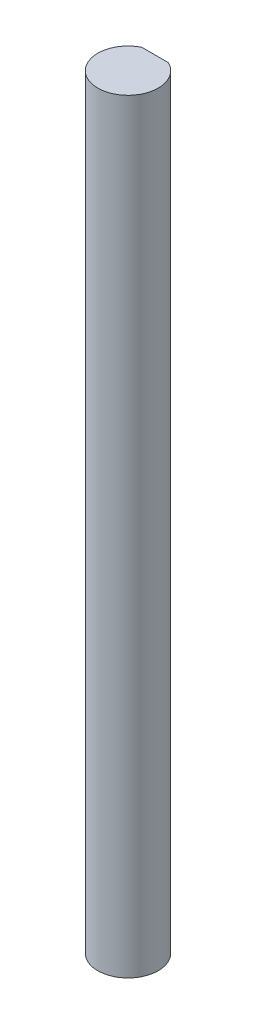
SolidWorks part; units mm, degrees
ref_plane "Front Plane" through (0, 0, 0) normal (0, 0, 1) x (1, 0, 0)
ref_plane "Top Plane" through (0, 0, 0) normal (0, 1, 0) x (1, 0, 0)
ref_plane "Right Plane" through (0, 0, 0) normal (1, 0, 0) x (0, 0, -1)
sketch "Sketch1" plane through (0, 0, 0) normal (0, 1, 0) x (1, 0, 0)
  line L1 (-1.0464, 2.1283) -> (1.0464, 2.1283)
  arc A0 (-1.0464, 2.1283) -> (1.0464, 2.1283) centre (0, 0) ccw
extrude "Boss-Extrude1" add sketch "Sketch1" along normal blind 60
